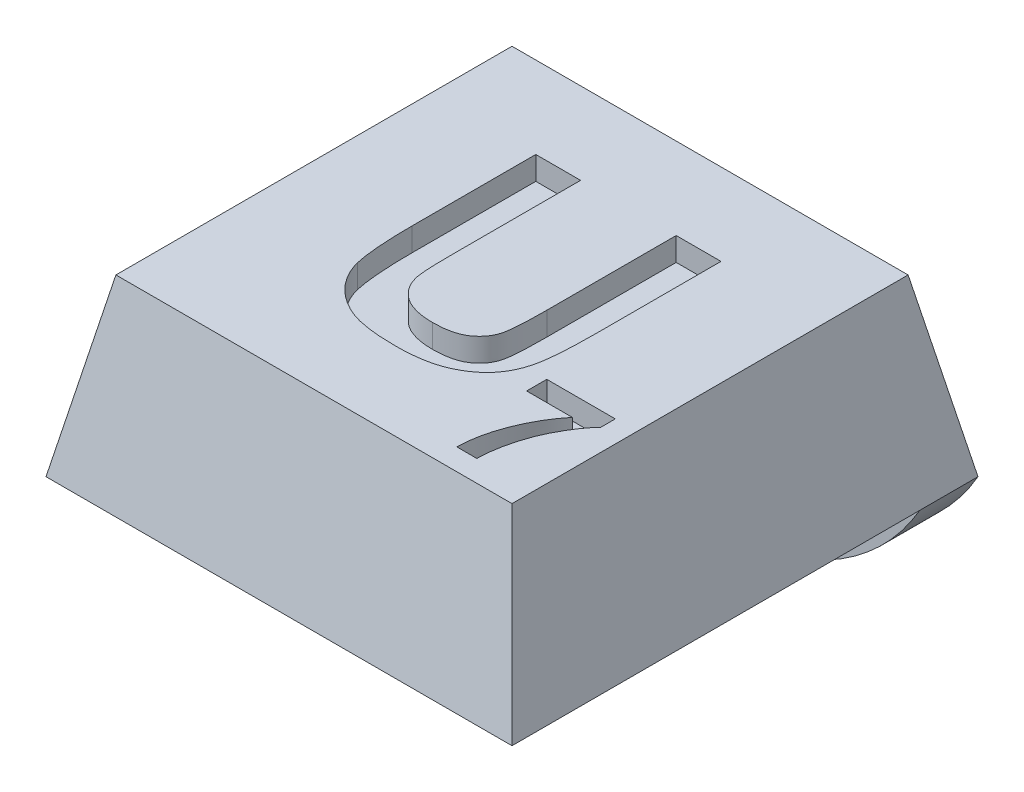
SolidWorks part; units mm, degrees
ref_plane "Front Plane" through (0, 0, 0) normal (0, 0, 1) x (1, 0, 0)
ref_plane "Top Plane" through (0, 0, 0) normal (0, 1, 0) x (1, 0, 0)
ref_plane "Right Plane" through (0, 0, 0) normal (1, 0, 0) x (0, 0, -1)
sketch "Sketch1" plane through (0, 0, 0) normal (0, 1, 0) x (1, 0, 0)
  line L1 (0, 0) -> (8, 0)
  line L2 (0, 0) -> (0, 8)
  line L3 (0, 8) -> (8, 8)
  line L4 (8, 0) -> (8, 8)
  dimension "D1" = 8
  dimension "D2" = 8
extrude "Boss-Extrude1" add sketch "Sketch1" along normal blind 3
sketch "Sketch2" plane through (0, 0, 0) normal (0, 0, 1) x (1, 0, 0)
  line L0 (0, 0) -> (0.6, 3)
  line L1 (0, 3) -> (8, 3) construction
  line L2 (0.6, 3) -> (0, 3)
  line L3 (0, 3) -> (0, 0)
  line L4 (8, 0) -> (7.4, 3)
  line L5 (7.4, 3) -> (8, 3)
  line L6 (8, 3) -> (8, 0)
  dimension "D1" = 0.6
  dimension "D2" = 0.6
extrude "Cut-Extrude1" cut sketch "Sketch2" against normal through all both and the other way through all
sketch "Sketch3" plane through (0, 0, 0) normal (1, 0, 0) x (0, 0, -1)
  line L0 (0, 0) -> (0.6, 3)
  line L1 (8, 3) -> (0, 3) construction
  line L2 (0.6, 3) -> (0, 3)
  line L3 (0, 3) -> (0, 0)
  line L4 (8, 3) -> (7.4, 3)
  line L5 (7.4, 3) -> (8, 0)
  line L6 (8, 3) -> (8, 0)
  dimension "D1" = 0.6
  dimension "D2" = 0.6
extrude "Cut-Extrude2" cut sketch "Sketch3" along normal blind 11
sketch "Sketch4" plane through (0, 0, 0) normal (0, -1, 0) x (1, 0, 0)
  line L0 (8, 0) -> (8, -8) construction
  line L3 (0, 0) -> (8, 0) construction
  circle A0 centre (4, -3.75) radius 1.8
  dimension "D1" = 3.6
  dimension "D2" = 4
  dimension "D3" = 3.75
extrude "Cut-Extrude3" cut sketch "Sketch4" against normal blind 0.8
sketch "Sketch5" plane through (0, 0, 0) normal (0, -1, 0) x (1, 0, 0)
  line L0 (8, 0) -> (8, -8) construction
  line L1 (0, -8) -> (8, -8)
  line L2 (0, -8) -> (0, -7)
  line L3 (0, -7) -> (8, -7)
  line L4 (8, -8) -> (8, -7)
  dimension "D1" = 1
extrude "Boss-Extrude2" add sketch "Sketch5" along normal blind 2
fillet "Fillet1" radius 4 2 edges at (8, -2, -7.5) (0, -2, -7.5)
sketch "Sketch6" plane through (0, 3, 0) normal (0, 1, 0) x (1, 0, 0)
  text T0 "U" font "Arial" height 4
extrude "Cut-Extrude4" cut sketch "Sketch6" against normal blind 0.4
sketch "Sketch7" plane through (0, 3, 0) normal (0, 1, 0) x (1, 0, 0)
  text T0 "7" font "Arial" height 1.8
extrude "Cut-Extrude5" cut sketch "Sketch7" against normal blind 0.4
